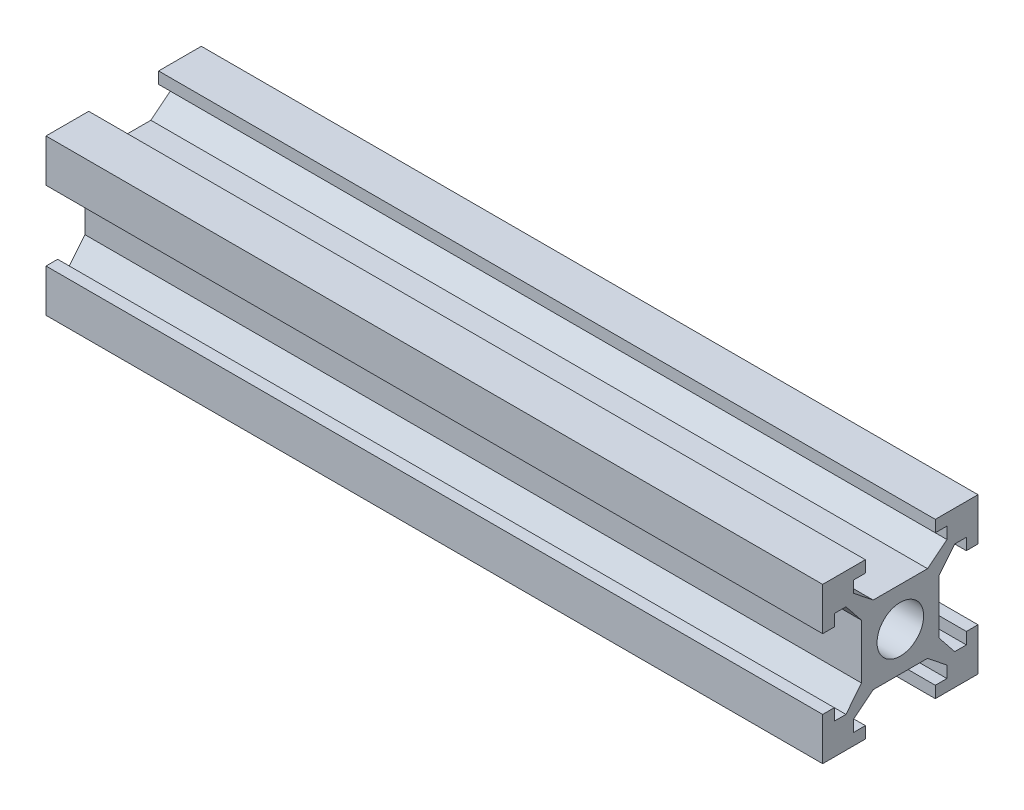
SolidWorks part; units mm, degrees
ref_plane "Front Plane" through (0, 0, 0) normal (0, 0, 1) x (1, 0, 0)
ref_plane "Top Plane" through (0, 0, 0) normal (0, 1, 0) x (1, 0, 0)
ref_plane "Right Plane" through (0, 0, 0) normal (1, 0, 0) x (0, 0, -1)
sketch "Sketch1" plane through (0, 0, 0) normal (1, 0, 0) x (0, 0, -1)
  line L1 (-10, 10) -> (10, 10)
  line L2 (-10, 10) -> (-10, -10)
  line L3 (-10, -10) -> (10, -10)
  line L4 (10, 10) -> (10, -10)
  line L5 (-10, 10) -> (10, -10) construction
  line L6 (-10, -10) -> (10, 10) construction
  point P0 (0, 0)
  dimension "D1" = 20
  dimension "D2" = 20
extrude "Boss-Extrude1" add sketch "Sketch1" along normal blind 100
sketch "Sketch2" plane through (100, 0, 0) normal (1, 0, 0) x (0, 0, -1)
  line L0 (0, 0) -> (0, 10) construction
  line L1 (10, 10) -> (-10, 10) construction
  line L2 (-4.5, 10) -> (-4.5, 8.5)
  line L3 (-4.5, 8.5) -> (-6, 8.5)
  line L4 (-6, 8.5) -> (-6, 7)
  line L5 (-6, 7) -> (-3.5, 5)
  line L6 (-3.5, 5) -> (3.5, 5)
  line L7 (-4.5, 10) -> (4.5, 10)
  line L8 (6, 7) -> (3.5, 5)
  line L9 (6, 8.5) -> (6, 7)
  line L10 (4.5, 8.5) -> (6, 8.5)
  line L11 (4.5, 10) -> (4.5, 8.5)
  circle A0 centre (0, 0) radius 3
  point P14 (0, 5)
  line M2 (10, 10) -> (-10, 10)
  dimension "D1" = 6
  dimension "D2" = 4.5
  dimension "D3" = 3.5
  dimension "D4" = 1.5
  dimension "D5" = 1.5
  dimension "D6" = 2
extrude "Cut-Extrude1" cut sketch "Sketch2" against normal through all contours A0 region at (100, 0, 0)
extrude "Cut-Extrude2" cut sketch "Sketch2<3>" against normal through all contours L0 L6 L8 L9 L10 L11 M2 | L6 L0 L7 L2 L3 L4 L5 region at (100, 7.5256, 2.585) region at (100, 7.5256, -2.585)
sketch "Sketch2<3>" plane through (100, 0, 0) normal (1, 0, 0) x (0, 0, -1) same geometry as "Sketch2"
pattern_circular "CirPattern1" count 4 every 90 about axis through (0, 0, 0) along (1, 0, 0) of "Cut-Extrude2"
